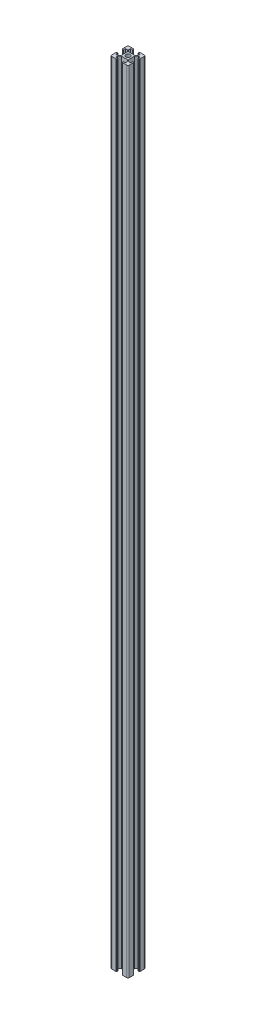
SolidWorks part; units mm, degrees
ref_plane "Front Plane" through (0, 0, 0) normal (0, 0, 1) x (1, 0, 0)
ref_plane "Top Plane" through (0, 0, 0) normal (0, 1, 0) x (1, 0, 0)
ref_plane "Right Plane" through (0, 0, 0) normal (1, 0, 0) x (0, 0, -1)
sketch "Sketch1" plane through (0, 0, 0) normal (0, 1, 0) x (1, 0, 0)
  line L0 (-8.5, 8.5) -> (8.5, 8.5)
  line L1 (-8.5, -10) -> (8.5, -10)
  line L2 (-10, -8.5) -> (-10, 8.5)
  line L3 (-8.5, 10) -> (8.5, 10)
  line L4 (10, -8.5) -> (10, 8.5)
  line L5 (-10, -10) -> (10, 10) construction
  line L6 (-10, 10) -> (10, -10) construction
  line L7 (8.5, -8.5) -> (8.5, 8.5)
  line L8 (-8.5, -8.5) -> (8.5, -8.5)
  line L9 (-8.5, -8.5) -> (-8.5, 8.5)
  line L10 (-10.4243, 9.5757) -> (9.5757, -10.4243)
  line L11 (-9.5757, -10.4243) -> (10.4243, 9.5757)
  line L12 (-9.5757, 10.4243) -> (10.4243, -9.5757)
  line L13 (-10.4243, -9.5757) -> (9.5757, 10.4243)
  line L14 (-9.5, -8.5) -> (-9.5, 8.5)
  line L15 (-10, -5.5) -> (10, -5.5)
  line L16 (-10, -5.5) -> (-10, 5.5)
  line L17 (-10, 5.5) -> (10, 5.5)
  line L18 (10, -5.5) -> (10, 5.5)
  line L19 (-10, -5.5) -> (10, 5.5) construction
  line L20 (-10, 5.5) -> (10, -5.5) construction
  line L21 (5.5, -10) -> (-5.5, -10)
  line L22 (5.5, -10) -> (5.5, 10)
  line L23 (5.5, 10) -> (-5.5, 10)
  line L24 (-5.5, -10) -> (-5.5, 10)
  line L25 (5.5, -10) -> (-5.5, 10) construction
  line L26 (5.5, 10) -> (-5.5, -10) construction
  line L27 (10, -3.1) -> (-10, -3.1)
  line L28 (10, -3.1) -> (10, 3.1)
  line L29 (10, 3.1) -> (-10, 3.1)
  line L30 (-10, -3.1) -> (-10, 3.1)
  line L31 (10, -3.1) -> (-10, 3.1) construction
  line L32 (10, 3.1) -> (-10, -3.1) construction
  line L33 (10, -3.6) -> (-10, -3.6)
  line L34 (10, -3.6) -> (10, 3.6)
  line L35 (10, 3.6) -> (-10, 3.6)
  line L36 (-10, -3.6) -> (-10, 3.6)
  line L37 (10, -3.6) -> (-10, 3.6) construction
  line L38 (10, 3.6) -> (-10, -3.6) construction
  line L39 (-8.5, 9.5) -> (8.5, 9.5)
  line L40 (9.5, -8.5) -> (9.5, 8.5)
  line L41 (-8.5, -9.5) -> (8.5, -9.5)
  arc A0 (-8.5, 10) -> (-10, 8.5) centre (-8.5, 8.5) ccw
  arc A1 (10, 8.5) -> (8.5, 10) centre (8.5, 8.5) ccw
  arc A2 (8.5, -10) -> (10, -8.5) centre (8.5, -8.5) ccw
  arc A3 (-10, -8.5) -> (-8.5, -10) centre (-8.5, -8.5) ccw
  arc A4 (8.5, 8.5) -> (8.5, 8.5) centre (8.5, 8.5) ccw
  arc A5 (8.5, -8.5) -> (8.5, -8.5) centre (8.5, -8.5) ccw
  arc A6 (-8.5, -8.5) -> (-8.5, -8.5) centre (-8.5, -8.5) ccw
  arc A7 (-8.5, 8.5) -> (-8.5, 8.5) centre (-8.5, 8.5) ccw
  circle A8 centre (0, 0) radius 2.5
  arc A9 (-8.5, 9.5) -> (-9.5, 8.5) centre (-8.5, 8.5) ccw
  arc A10 (9.5, 8.5) -> (8.5, 9.5) centre (8.5, 8.5) ccw
  arc A11 (8.5, -9.5) -> (9.5, -8.5) centre (8.5, -8.5) ccw
  arc A12 (-9.5, -8.5) -> (-8.5, -9.5) centre (-8.5, -8.5) ccw
  point P0 (0, 0)
  point P38 (0, 0)
  point P43 (0, 0)
  dimension "D3" = 1.5
  dimension "D4" = 1.5
  dimension "D5" = 1.5
  dimension "D6" = 1.5
  dimension "D12" = 5
  dimension "D1" = 20
  dimension "D2" = 20
  dimension "D10" = 11
  dimension "D11" = 11
  dimension "D13" = 6.2
  dimension "D14" = 7.2
  dimension "D7" = 1.5
  dimension "D8" = 0.6
  dimension "D9" = 0.6
  dimension "D15" = 0.5
sketch "Sketch2" plane through (0, 0, 0) normal (0, 1, 0) x (1, 0, 0)
  line L0 (-10, -8.5) -> (-10, 8.5) construction
  line L1 (-8.5, 10) -> (8.5, 10) construction
  line L2 (10, -8.5) -> (10, 8.5) construction
  line L3 (-8.5, -10) -> (8.5, -10) construction
  line L4 (-10, -8.5) -> (-10, 8.5)
  line L5 (-8.5, 10) -> (8.5, 10)
  line L6 (10, -8.5) -> (10, 8.5)
  line L7 (-8.5, -10) -> (8.5, -10)
  arc A0 (-8.5, 10) -> (-10, 8.5) centre (-8.5, 8.5) ccw construction
  arc A1 (10, 8.5) -> (8.5, 10) centre (8.5, 8.5) ccw construction
  arc A2 (8.5, -10) -> (10, -8.5) centre (8.5, -8.5) ccw construction
  arc A3 (-10, -8.5) -> (-8.5, -10) centre (-8.5, -8.5) ccw construction
  arc A4 (-8.5, 10) -> (-10, 8.5) centre (-8.5, 8.5) ccw
  arc A5 (10, 8.5) -> (8.5, 10) centre (8.5, 8.5) ccw
  arc A6 (8.5, -10) -> (10, -8.5) centre (8.5, -8.5) ccw
  arc A7 (-10, -8.5) -> (-8.5, -10) centre (-8.5, -8.5) ccw
extrude "Boss-Extrude1" add sketch "Sketch2" along normal blind 900
sketch "Sketch3" plane through (0, 900, 0) normal (0, 1, 0) x (1, 0, 0)
  line L3 (4.2, -4.2) -> (-4.2, -4.2)
  line L4 (4.2, -4.2) -> (4.2, 4.2)
  line L5 (4.2, 4.2) -> (-4.2, 4.2)
  line L6 (-4.2, -3.3515) -> (-4.2, 3.3515)
  line L7 (4.2, -4.2) -> (-4.2, 4.2) construction
  line L8 (4.2, 4.2) -> (-4.2, -4.2) construction
  line L10 (-10.4243, 9.5757) -> (9.5757, -10.4243) construction
  line L11 (-9.5757, 10.4243) -> (10.4243, -9.5757) construction
  line L12 (-10.4243, 9.5757) -> (-4.2, 3.3515)
  line L13 (-9.5757, 10.4243) -> (10.4243, -9.5757)
  line L15 (-8.5, -8.5) -> (-8.5, 8.5) construction
  line L16 (-8.5, -8.5) -> (-8.5, -3.1)
  line L17 (-10, 5.5) -> (10, 5.5) construction
  line L19 (10, -3.1) -> (-10, -3.1) construction
  line L20 (10, -3.6) -> (-10, -3.6) construction
  line L22 (10, 3.6) -> (-10, 3.6) construction
  line L23 (-10, -8.5) -> (-10, 8.5) construction
  line L24 (-10.4243, -9.5757) -> (9.5757, 10.4243) construction
  line L25 (-8.5, 5.5) -> (10, 5.5)
  line L26 (-10, -5.5) -> (10, -5.5) construction
  line L27 (10, -3.1) -> (-4.2, -3.1)
  line L28 (10, -3.6) -> (-4.4485, -3.6)
  line L29 (-10, -5.5) -> (10, -5.5)
  line L30 (10, 3.6) -> (-4.4485, 3.6)
  line L31 (-10, -8.5) -> (-10, -3.8)
  line L32 (-10.4243, -9.5757) -> (-4.2, -3.3515)
  line L33 (-10, 3.8) -> (-10, 8.5)
  line L34 (10, 3.1) -> (-10, 3.1) construction
  line L35 (10, 3.1) -> (-4.2, 3.1)
  line L36 (-9.5, -3.6) -> (-9.8, -3.6)
  line L37 (-8.5, -3.1) -> (-9.3, -3.1)
  line L38 (-9.5, 3.3) -> (-9.5, 3.6)
  line L39 (-8.5, 3.1) -> (-8.5, 8.5)
  line L40 (-9.5, 3.6) -> (-9.8, 3.6)
  line L41 (-9.5, -3.6) -> (-9.5, -3.3)
  line L42 (4.6515, -5.5) -> (10, -5.5)
  line L43 (-8.5, 3.1) -> (-9.3, 3.1)
  line L44 (-9.5, -8.5) -> (-9.5, 8.5) construction
  line L45 (-10, -8.5) -> (-10, 8.5)
  arc A0 (-9.8, -3.6) -> (-10, -3.8) centre (-9.8, -3.8) ccw
  arc A1 (-9.3, -3.1) -> (-9.5, -3.3) centre (-9.3, -3.3) ccw
  arc A2 (-9.5, 3.3) -> (-9.3, 3.1) centre (-9.3, 3.3) ccw
  arc A3 (-10, 3.8) -> (-9.8, 3.6) centre (-9.8, 3.8) ccw
  circle A6 centre (0, 0) radius 2.5 construction
  circle A7 centre (0, 0) radius 2.5
  point P0 (0, 0)
  point P55 (-9.5, 3.1)
  line M12 (-10, 8.5) -> (-10, -8.5)
  dimension "D2" = 0.2
  dimension "D3" = 0.2
  dimension "D4" = 0.2
  dimension "D5" = 0.2
  dimension "D7" = 4.3
extrude "Cut-Extrude1" cut sketch "Sketch3" against normal through all contours L39 L43 L38 L40 L36 L41 L37 L16 L29 L32 L6 L12 L25 M12 | L13 A7 | L13 A7 region at (-7.0241, 900, 0) region at (-0.5269, 900, 0.5269) region at (0.9842, 900, -0.9842)
ref_axis "Axis1" through (0, -20, 0) along (0, 1, 0)
pattern_circular "CirPattern1" count 4 over 360 about axis through (0, -20, 0) along (0, 1, 0) of "Cut-Extrude1"
sketch "Sketch4" plane through (0, 900, 0) normal (0, 1, 0) x (1, 0, 0)
sketch "Sketch5" plane through (0, 900, 0) normal (0, 1, 0) x (1, 0, 0)
  line L0 (-8.5, 3.1) -> (-9.3, 3.1) construction
  line L1 (-8.5, -3.1) -> (-9.3, -3.1) construction
  dimension "D1" = 6.2
